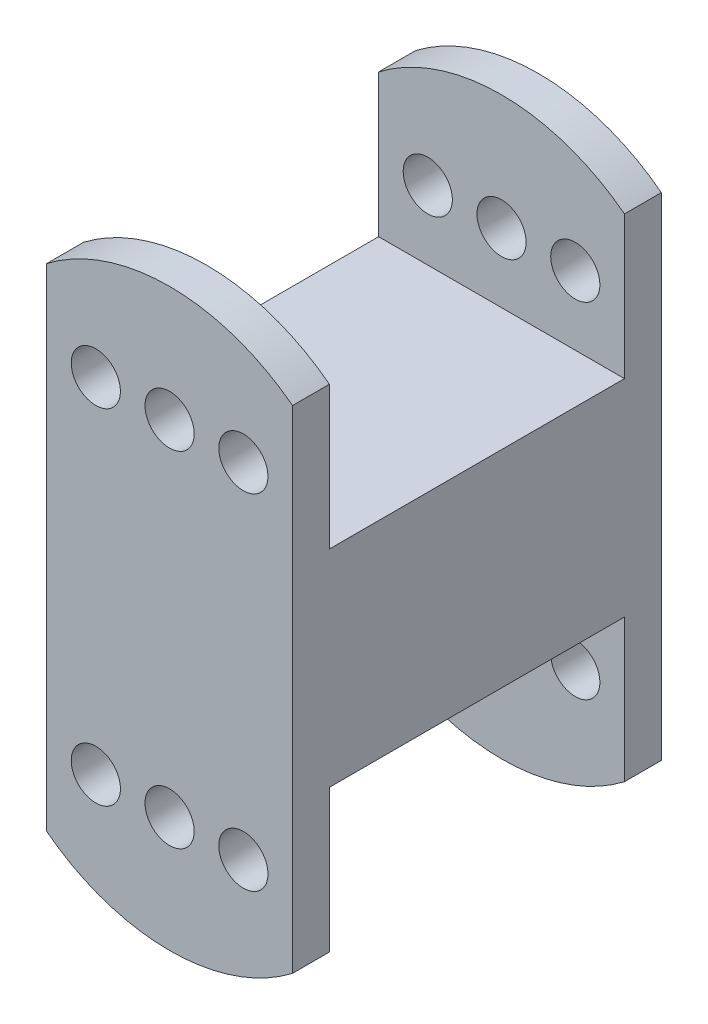
SolidWorks part; units mm, degrees
ref_plane "Front Plane" through (0, 0, 0) normal (0, 0, 1) x (1, 0, 0)
ref_plane "Top Plane" through (0, 0, 0) normal (0, 1, 0) x (1, 0, 0)
ref_plane "Right Plane" through (0, 0, 0) normal (1, 0, 0) x (0, 0, -1)
sketch "Sketch1" plane through (0, 0, 0) normal (0, 0, 1) x (1, 0, 0)
  line L0 (0, 0) -> (-10, -13.0323) construction
  line L1 (0, 0) -> (10, -13.0323) construction
  line L2 (-10, -13.0323) -> (10, -13.0323) construction
  line L3 (-10, -13.0323) -> (-10, 26.9677)
  line L5 (10, 26.9677) -> (10, -13.0323)
  line L6 (0, 13.9355) -> (10, 26.9677) construction
  line L7 (-10, 26.9677) -> (0, 13.9355) construction
  line L8 (-10, 26.9677) -> (10, 26.9677) construction
  line L9 (-10, 6.9677) -> (10, 6.9677) construction
  arc A0 (-10, -13.0323) -> (10, -13.0323) centre (0, 0) ccw
  arc A1 (-10, 26.9677) -> (10, 26.9677) centre (0, 13.9355) cw
  circle A2 centre (0, -7.0323) radius 2
  circle A3 centre (6, -7.0323) radius 2
  circle A4 centre (-6, -7.0323) radius 2
  circle A5 centre (6, 20.9677) radius 2
  circle A6 centre (0, 20.9677) radius 2
  circle A7 centre (-6, 20.9677) radius 2
  dimension "D6" = 4
  dimension "D7" = 4
  dimension "D10" = 4
  dimension "D1" = 75
  dimension "D2" = 20
  dimension "D3" = 75
  dimension "D4" = 40
  dimension "D5" = 6
  dimension "D8" = 6
  dimension "D9" = 6
extrude "Boss-Extrude1" add sketch "Sketch1" along normal blind 30
sketch "Sketch2" plane through (10, 0, 0) normal (1, 0, 0) x (0, 0, -1)
  line L0 (-30, -16.4268) -> (0, -16.4268) construction
  line L1 (-27, -16.4268) -> (-3, -16.4268)
  line L2 (-27, -16.4268) -> (-27, -1.4268)
  line L3 (-27, -1.4268) -> (-3, -1.4268)
  line L4 (-3, -16.4268) -> (-3, -1.4268)
  line L5 (-30, 6.9677) -> (0, 6.9677) construction
  line L6 (-30, -13.0323) -> (-30, 26.9677) construction
  line L7 (0, -13.0323) -> (0, 26.9677) construction
  line L8 (-27, 15.3623) -> (-3, 15.3623)
  line L9 (-3, 30.3623) -> (-3, 15.3623)
  line L10 (-27, 30.3623) -> (-3, 30.3623)
  line L11 (-27, 30.3623) -> (-27, 15.3623)
  dimension "D1" = 3
  dimension "D2" = 3
  dimension "D3" = 15
extrude "Cut-Extrude1" cut sketch "Sketch2" against normal through all
